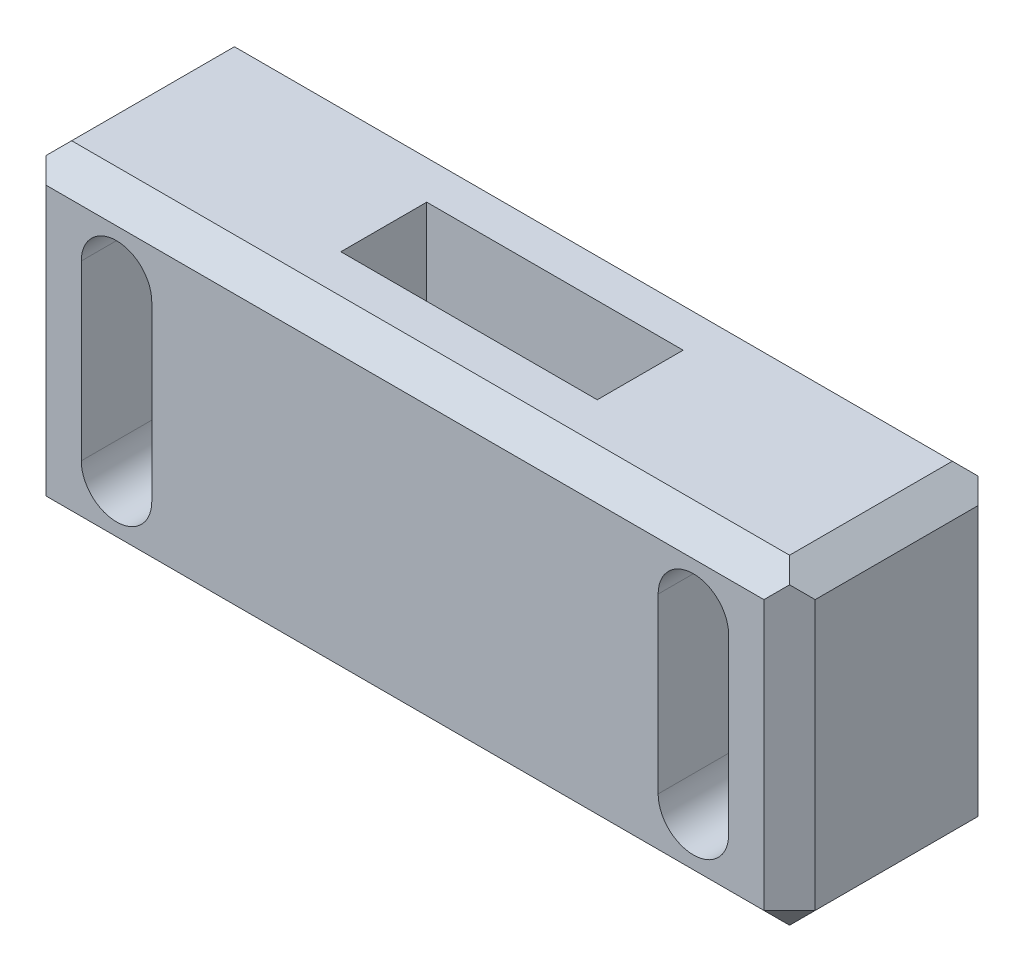
SolidWorks part; units mm, degrees
ref_plane "Front Plane" through (0, 0, 0) normal (0, 0, 1) x (1, 0, 0)
ref_plane "Top Plane" through (0, 0, 0) normal (0, 1, 0) x (1, 0, 0)
ref_plane "Right Plane" through (0, 0, 0) normal (1, 0, 0) x (0, 0, -1)
sketch "Sketch1" plane through (0, 0, 0) normal (0, 1, 0) x (1, 0, 0)
  line L5 (0, 0) -> (30, 0)
  line L6 (0, 0) -> (0, 16.7)
  line L7 (0, 16.7) -> (30, 16.7)
  line L8 (30, 0) -> (30, 16.7)
  line L10 (0, 0) -> (30, 16.7) construction
  line L11 (5, 6) -> (25, 6)
  line L12 (25, 5) -> (5, 5)
  line L13 (25, 5) -> (25, 11.7)
  line L14 (25, 11.7) -> (5, 11.7)
  line L15 (5, 5) -> (5, 11.7)
  line L16 (25, 5) -> (5, 11.7) construction
  line L17 (25, 11.7) -> (5, 5) construction
  line L18 (25, 10.7) -> (5, 10.7)
  line L19 (5, 11.7) -> (25, 10.7) construction
  line L20 (25, 5) -> (5, 6) construction
  point P10 (15, 8.35)
  dimension "D1" = 5
  dimension "D2" = 5
  dimension "D3" = 20
  dimension "D4" = 1
  dimension "D5" = 6.7
extrude "Boss-Extrude1" add sketch "Sketch1" along normal blind 25 contours L5 L8 L7 L6 L12 L15 L14 L13 region at (0.3433, 0, -8.35)
extrude "Boss-Extrude2" add sketch "Sketch1<3>" along normal offset from surface (13 mm away) 12 contours L18 L13 L14 L15 | L15 L12 L13 L11 region at (15, 0, -5.5) region at (15, 0, -11.2) up to face at (15, 25, -8.35)
sketch "Sketch1<3>" plane through (0, 0, 0) normal (0, 1, 0) x (1, 0, 0) same geometry as "Sketch1"
sketch "Sketch2" plane through (0, 0, -16.7) normal (0, 0, -1) x (-1, 0, 0)
  line L0 (0, 25) -> (0, 0) construction
  line L1 (-30, 25) -> (-45, 25)
  line L2 (-30, 25) -> (-30, 0)
  line L3 (-30, 0) -> (-45, 0)
  line L4 (-45, 25) -> (-45, 0)
  line L5 (0, 25) -> (15, 25)
  line L6 (0, 25) -> (0, 0)
  line L7 (0, 0) -> (15, 0)
  line L8 (15, 25) -> (15, 0)
  line L9 (0, 25) -> (-30, 25) construction
  line L10 (0, 0) -> (-30, 0) construction
  line L11 (-37.5, 5.75) -> (-37.5, 19.25) construction
  line L12 (-40.25, 5.75) -> (-40.25, 19.25)
  line L13 (-34.75, 5.75) -> (-34.75, 19.25)
  line L14 (-15, 25) -> (-15, 0) construction
  line L15 (7.5, 5.75) -> (7.5, 19.25) construction
  line L16 (10.25, 5.75) -> (10.25, 19.25)
  line L17 (4.75, 5.75) -> (4.75, 19.25)
  arc A0 (-40.25, 5.75) -> (-34.75, 5.75) centre (-37.5, 5.75) ccw
  arc A1 (-34.75, 19.25) -> (-40.25, 19.25) centre (-37.5, 19.25) ccw
  arc A2 (10.25, 5.75) -> (4.75, 5.75) centre (7.5, 5.75) cw
  arc A3 (4.75, 19.25) -> (10.25, 19.25) centre (7.5, 19.25) cw
  point P17 (-37.5, 12.5)
  point P25 (-37.5, 0)
  point P28 (7.5, 12.5)
  dimension "D1" = 15
  dimension "D2" = 5.5
  dimension "D3" = 5.75
  dimension "D4" = 5.75
extrude "Boss-Extrude3" add sketch "Sketch2" against normal through all
chamfer "Chamfer1" distance 2 angle 45 4 edges at (15, 25, 0) (15, 25, -16.7) (45, 25, -8.35) (-15, 25, -8.35)
chamfer "Chamfer2" distance 2 angle 45 12 edges at (15, 0, -10.7) (25, 0, -8.35) (15, 0, -6) (5, 0, -8.35) (45, 0, -8.35) (45, 11.5, 0) (15, 0, 0) (-15, 11.5, 0) (-15, 0, -8.35) (-15, 11.5, -16.7) (15, 0, -16.7) (45, 11.5, -16.7)
